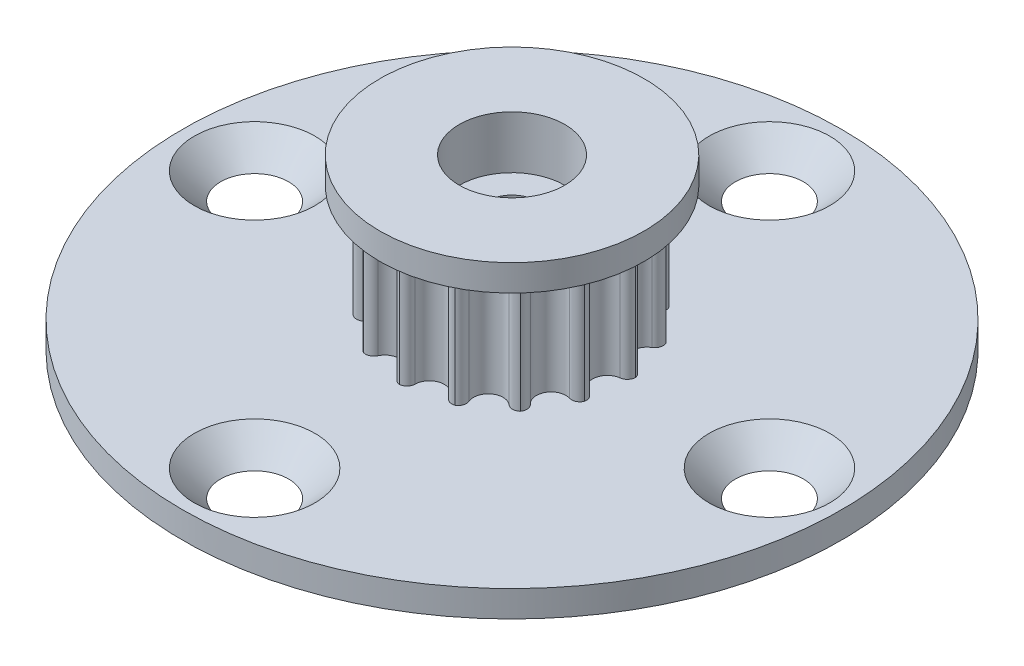
SolidWorks part; units mm, degrees
ref_plane "Front Plane" through (0, 0, 0) normal (0, 0, 1) x (1, 0, 0)
ref_plane "Top Plane" through (0, 0, 0) normal (0, 1, 0) x (1, 0, 0)
ref_plane "Right Plane" through (0, 0, 0) normal (1, 0, 0) x (0, 0, -1)
sketch "Sketch1" plane through (0, 0, 0) normal (0, 1, 0) x (1, 0, 0)
  line L0 (0, 0) -> (0, 6.7802) construction
  line L1 (0, 0) -> (2.6235, 5.8925) construction
  circle A0 centre (0, 0) radius 6.7802 construction
  circle A1 centre (0, 0) radius 5.5602 construction
  circle A2 centre (0, 6.4502) radius 0.89 construction
  circle A5 centre (2.6235, 5.8925) radius 0.89 construction
  arc A6 (0, 5.5602) -> (0.8665, 6.2469) centre (0, 6.4502) ccw
  arc A7 (0.8665, 6.2469) -> (1.461, 6.6209) centre (1.3532, 6.1327) cw
  arc A8 (1.3583, 6.6427) -> (1.7493, 6.0592) centre (1.2581, 6.1529) cw
  arc A9 (2.2615, 5.0795) -> (1.7493, 6.0592) centre (2.6235, 5.8925) cw
  arc A10 (1.461, 6.6209) -> (1.3583, 6.6427) centre (0, 0) cw
  arc A11 (0, 5.5602) -> (2.2615, 5.0795) centre (0, 0) ccw
  dimension "D1" = 13.5604
  dimension "D3" = 1.78
  dimension "D4" = 0.5
  dimension "D2" = 1.22
  dimension "D5" = 24
extrude "Boss-Extrude1" add sketch "Sketch1" along normal mid plane 7.112 contours A6 A11 A9 A8 A7 region at (0.0156, 0, -0.0736)
ref_axis "Axis1" through (0, 3.3, 0) along (0, -1, 0)
pattern_circular "CirPattern1" count 15 over 360 about axis through (0, 3.3, 0) along (0, -1, 0) of "Boss-Extrude1"
sketch "Sketch2" plane through (0, 0, 0) normal (1, 0, 0) x (0, 0, -1)
  line L10 (0, 3.5) -> (7.9549, 3.5) construction
  line L11 (0, 3.5) -> (0, 5.0875) construction
  line L12 (0, 5.0875) -> (7.9549, 5.0875) construction
  line L15 (7.9549, 3.5) -> (7.9549, 5.0875) construction
  line L20 (0, 3.3) -> (0, -3.3) construction
  line L22 (7.9549, 5.0875) -> (0, 5.0875)
  line L23 (7.9549, 5.0875) -> (7.9549, 3.5)
  line L24 (7.9549, 3.5) -> (0, 3.5)
  line L25 (0, 5.0875) -> (0, 3.5)
  dimension "D1" = 1.5875
  dimension "D2" = 7.9549
  dimension "D3" = 3.5
revolve "Revolve3" add sketch "Sketch2" angle 360 about axis through (0, 3.3, 0) along (0, -1, 0) region at (0, 4.2937, -3.9775)
mirror "Mirror1" about plane through (0, 0, 0) normal (0, 1, 0) of "Revolve3"
sketch "Sketch9" plane through (0, -5.0875, 0) normal (0, -1, 0) x (1, 0, 0)
  circle A0 centre (0, 0) radius 19.8438
  circle A1 centre (0, 0) radius 1.5
  dimension "D1" = 3
  dimension "D2" = 39.6875
extrude "Boss-Extrude2" add sketch "Sketch9" against normal up to surface (1.5875 mm away) up to face at (0, -3.5, 0)
sketch "Sketch3" plane through (0, 0, 0) normal (0, 1, 0) x (1, 0, 0)
  circle A0 centre (-15.5, 0) radius 1.7462
  circle A3 centre (0, 15.5) radius 1.7462
  circle A4 centre (15.5, 0) radius 1.7463
  circle A5 centre (0, -15.5) radius 1.7462
  dimension "D3" = 3.4925
  dimension "D1" = 15.5
  dimension "D4" = 4
extrude "Cut-Extrude1" cut sketch "Sketch3" against normal through all both and the other way through all
ref_axis "Axis2" through (-15.5, -5.0875, 0) along (0, 1, 0)
sketch "Sketch6" plane through (0, 0, 0) normal (0, 0, 1) x (1, 0, 0)
  line L0 (-19.1322, -3.5) -> (-11.8678, -3.5) construction
  line L1 (-13.7538, -3.5) -> (-17.2462, -3.5) construction
  line L2 (-11.8678, -3.5) -> (-15.5, -7.1322)
  line L3 (-15.5, -7.1322) -> (-19.1322, -3.5) construction
  line L4 (-18.548, -4.0842) -> (-12.452, -4.0842) construction
  line L5 (-17.2462, -3.998) -> (-13.7538, -3.998) construction
  line L8 (-15.5, -7.1322) -> (-15.5, -3.5)
  line L9 (-15.5, -3.5) -> (-11.8678, -3.5)
  line L10 (-15.5, -5.0875) -> (-15.5, -3.5) construction
  line L12 (-17.2462, -3.5) -> (-17.2462, -5.0875) construction
  line L13 (-13.7538, -5.0875) -> (-13.7538, -3.5) construction
  point P2 (-15.5, -3.998)
  dimension "D1" = 6.096
  dimension "D2" = 0.5842
revolve "Cut-Revolve2" cut sketch "Sketch6" angle 360 about axis through (-15.5, -5.0875, 0) along (0, 1, 0)
pattern_circular "CirPattern2" count 4 over 360 about axis through (0, 3.3, 0) along (0, -1, 0) of "Cut-Revolve2"
sketch "Sketch12" plane through (0, 5.0875, 0) normal (0, 1, 0) x (1, 0, 0)
  circle A0 centre (0, 0) radius 3.175
  dimension "D1" = 6.35
extrude "Cut-Extrude2" cut sketch "Sketch12" against normal blind 3.175 from surface starting at face at (0, 5.0875, 7.9549)
sketch "Sketch13" plane through (0, 1.9125, 0) normal (0, 1, 0) x (1, 0, 0)
  circle A0 centre (0, 0) radius 1.525
  dimension "D1" = 3.05
extrude "Cut-Extrude4" cut sketch "Sketch13" against normal through all contours A0
equation "\"TEETH_NUM\" = 15"
equation "\"TOOTH_PITCH\"= 3mm"
equation "\"PITCH_LINE_OFFSET\"= .015in"
equation "\"DIAMETER_PER_GROOVE\"= \"OUTSIDE_DIAMETER\" / \"TEETH_NUM\" * 1in"
equation "\"PITCH_DIAMETER\"= ( ( \"TEETH_NUM\" * 3 - 1.31 ) / 3.1415 + .415 ) * 1mm"
equation "\"OUTSIDE_DIAMETER\"= \"PITCH_DIAMETER\" - \"PITCH_LINE_OFFSET\" * 2"
equation "\"D1@Sketch1\"=\"OUTSIDE_DIAMETER\""
equation "\"TOOTH_HEIGHT\"= 1.22mm"
equation "\"D2@Sketch1\"=\"TOOTH_HEIGHT\""
equation "\"TOOTH_DIAMETER\"= 1.78mm"
equation "\"INTERNAL_RADIUS\"= .5mm"
equation "\"D3@Sketch1\"=\"TOOTH_DIAMETER\""
equation "\"D5@Sketch1\"=360 / \"TEETH_NUM\""
equation "\"D4@Sketch1\"=\"INTERNAL_RADIUS\""
equation "\"D1@CirPattern1\"=\"TEETH_NUM\""
equation "\"BELT_GAP\"= 7mm"
equation "\"D2@Sketch2\"=\"PITCH_DIAMETER\"/2+1/32"
equation "\"D3@Sketch2\"=\"BELT_GAP\"/2"
